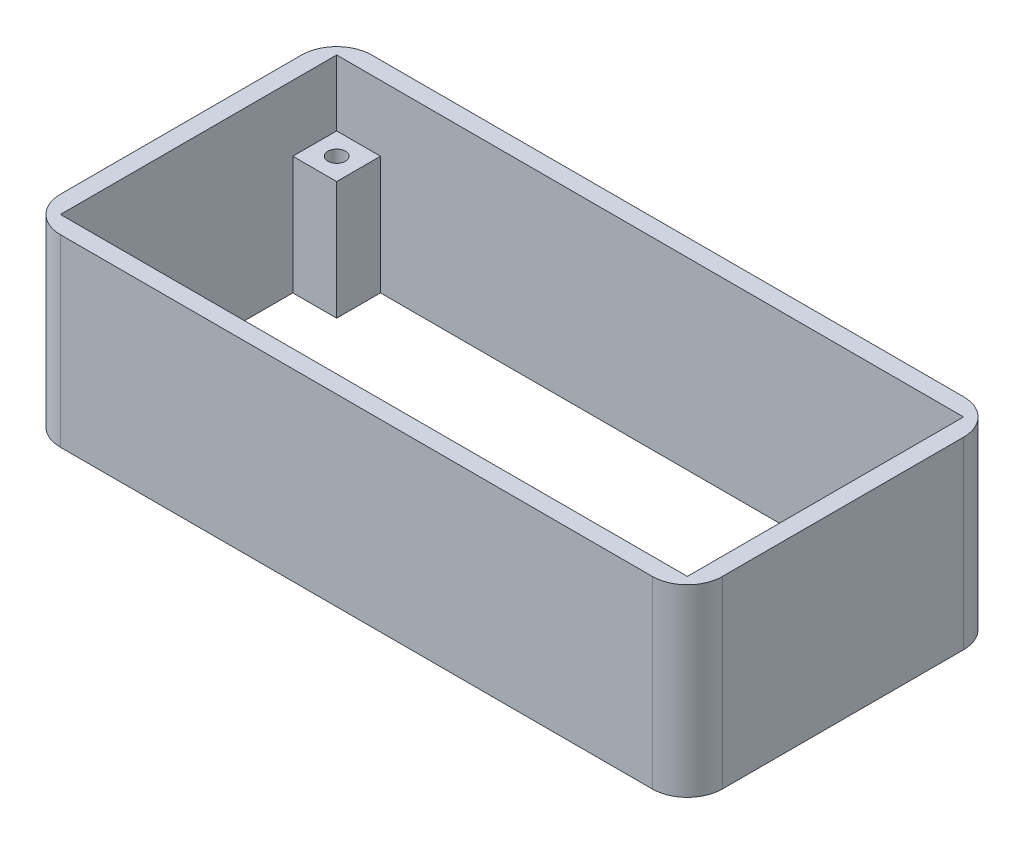
SolidWorks part; units mm, degrees
ref_plane "Front Plane" through (0, 0, 0) normal (0, 0, 1) x (1, 0, 0)
ref_plane "Top Plane" through (0, 0, 0) normal (0, 1, 0) x (1, 0, 0)
ref_plane "Right Plane" through (0, 0, 0) normal (1, 0, 0) x (0, 0, -1)
sketch "Sketch1" plane through (0, 0, 0) normal (0, 1, 0) x (1, 0, 0)
  line L1 (-94.7084, 26.452) -> (48.2916, 26.452)
  line L2 (-94.7084, 26.452) -> (-94.7084, -36.548)
  line L3 (-94.7084, -36.548) -> (48.2916, -36.548)
  line L4 (48.2916, 26.452) -> (48.2916, -36.548)
  line L5 (-90.7084, 30.452) -> (44.2916, 30.452)
  line L6 (-98.7084, 22.452) -> (-98.7084, -32.548)
  line L7 (-90.7084, -40.548) -> (44.2916, -40.548)
  line L8 (52.2916, 22.452) -> (52.2916, -32.548)
  line L9 (-94.7084, -26.548) -> (-84.7084, -26.548)
  line L10 (-94.7084, -26.548) -> (-94.7084, -36.548)
  line L11 (-94.7084, -36.548) -> (-84.7084, -36.548)
  line L12 (-84.7084, -26.548) -> (-84.7084, -36.548)
  line L13 (-94.7084, 16.452) -> (-84.7084, 16.452)
  line L14 (-94.7084, 16.452) -> (-94.7084, 26.452)
  line L15 (-94.7084, 26.452) -> (-84.7084, 26.452)
  line L16 (-84.7084, 16.452) -> (-84.7084, 26.452)
  line L17 (38.2916, 26.452) -> (48.2916, 26.452)
  line L18 (38.2916, 26.452) -> (38.2916, 16.452)
  line L19 (38.2916, 16.452) -> (48.2916, 16.452)
  line L20 (48.2916, 26.452) -> (48.2916, 16.452)
  line L21 (38.2916, -36.548) -> (48.2916, -36.548)
  line L22 (38.2916, -36.548) -> (38.2916, -26.548)
  line L23 (38.2916, -26.548) -> (48.2916, -26.548)
  line L24 (48.2916, -36.548) -> (48.2916, -26.548)
  arc A0 (-90.7084, 30.452) -> (-98.7084, 22.452) centre (-90.7084, 22.452) ccw
  arc A1 (52.2916, 22.452) -> (44.2916, 30.452) centre (44.2916, 22.452) ccw
  arc A2 (44.2916, -40.548) -> (52.2916, -32.548) centre (44.2916, -32.548) ccw
  arc A3 (-98.7084, -32.548) -> (-90.7084, -40.548) centre (-90.7084, -32.548) ccw
  circle A4 centre (43.2916, 21.452) radius 2
  circle A5 centre (43.2916, -31.548) radius 2
  circle A6 centre (-89.7084, -31.548) radius 2
  circle A7 centre (-89.7084, 21.452) radius 2
  dimension "D3" = 8
  dimension "D4" = 8
  dimension "D5" = 8
  dimension "D6" = 8
  dimension "D19" = 4
  dimension "D22" = 4
  dimension "D25" = 4
  dimension "D28" = 4
  dimension "D1" = 63
  dimension "D2" = 143
  dimension "D7" = 4
  dimension "D8" = 4
  dimension "D9" = 4
  dimension "D10" = 4
  dimension "D11" = 10
  dimension "D12" = 10
  dimension "D13" = 10
  dimension "D14" = 10
  dimension "D15" = 10
  dimension "D16" = 10
  dimension "D17" = 10
  dimension "D18" = 10
  dimension "D20" = 5
  dimension "D21" = 5
  dimension "D23" = 5
  dimension "D24" = 5
  dimension "D26" = 5
  dimension "D27" = 5
  dimension "D29" = 5
  dimension "D30" = 5
extrude "Boss-Extrude5" add sketch "Sketch1" along normal blind 27 contours L13 L16 L1 L2 A7 | L12 L9 L2 L3 A6 | L23 L22 L3 L4 A5 | L18 L19 L4 L1 A4 region at (-89.7084, 0, -26.3106) region at (43.2916, 0, -26.3106) region at (-89.7084, 0, 26.6894) region at (48.1502, 0, 31.548)
extrude "Boss-Extrude6" add sketch "Sketch1<7>" along normal blind 42 contours L6 A3 L7 A2 L8 A1 L5 A0 L1 L4 L3 L2 region at (-23.2084, 0, -28.7834)
sketch "Sketch1<7>" plane through (0, 0, 0) normal (0, 1, 0) x (1, 0, 0) same geometry as "Sketch1"
